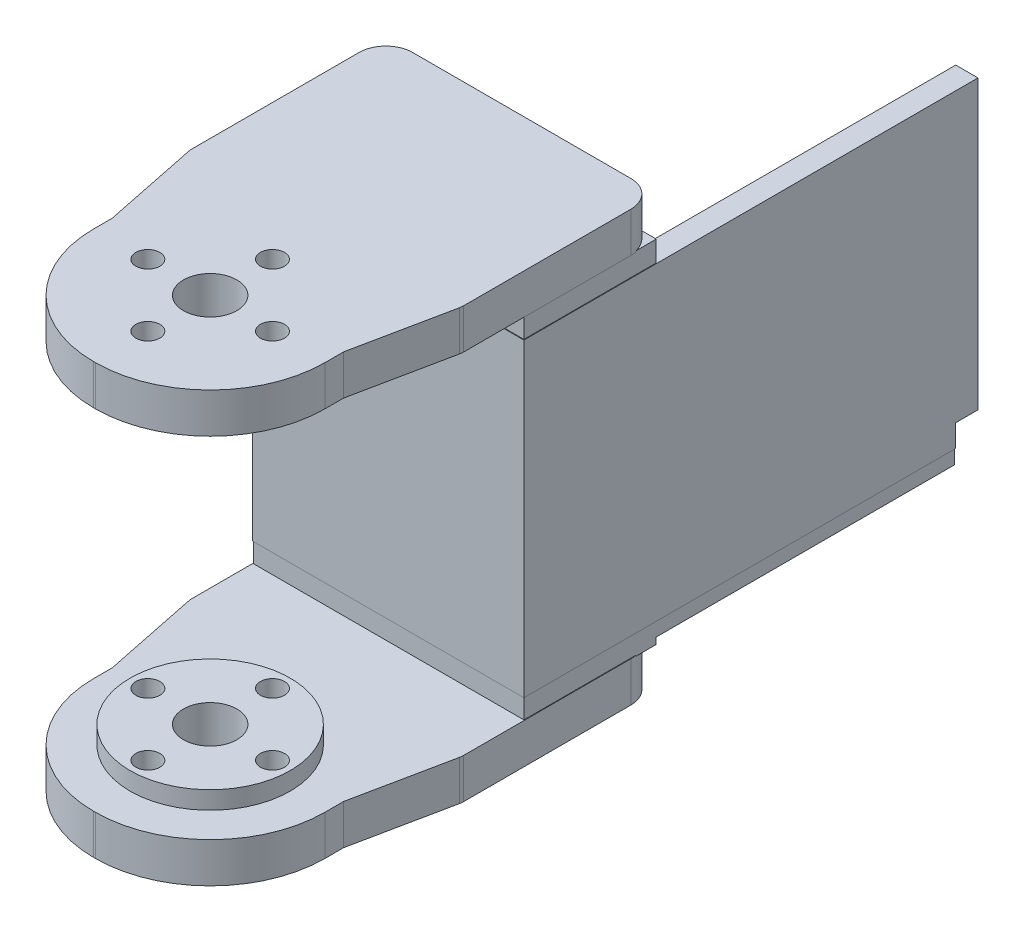
SolidWorks part; units mm, degrees
ref_plane "Front Plane" through (0, 0, 0) normal (0, 0, 1) x (1, 0, 0)
ref_plane "Top Plane" through (0, 0, 0) normal (0, 1, 0) x (1, 0, 0)
ref_plane "Right Plane" through (0, 0, 0) normal (1, 0, 0) x (0, 0, -1)
ref_plane "PY_p18_625" through (0, 18.625, 0) normal (0, 1, 0) x (1, 0, 0)
sketch "S_prism1" plane through (0, 18.625, 0) normal (0, 1, 0) x (1, 0, 0)
  line L0 (-13, 2) -> (-15.2191, 12.8008)
  line L1 (-15.26, 13.2033) -> (-15.26, 32)
  line L2 (-12.26, 35) -> (12.26, 35)
  line L3 (15.26, 32) -> (15.26, 13.2033)
  line L4 (15.2191, 12.8008) -> (13, 2)
  line L5 (13, 2) -> (13, -0.1)
  line L6 (0.1, -13) -> (-0.1, -13)
  line L7 (-13, -0.1) -> (-13, 2)
  arc A0 (-15.2191, 12.8008) -> (-15.26, 13.2033) centre (-13.2498, 13.2042) cw
  arc A1 (-15.26, 32) -> (-12.26, 35) centre (-12.2599, 31.9999) cw
  arc A2 (12.26, 35) -> (15.26, 32) centre (12.2599, 31.9999) cw
  arc A3 (15.26, 13.2033) -> (15.2191, 12.8008) centre (13.2498, 13.2042) cw
  arc A4 (13, -0.1) -> (0.1, -13) centre (0.1001, -0.1001) cw
  arc A5 (-0.1, -13) -> (-13, -0.1) centre (-0.1001, -0.1001) cw
extrude "Boss_1" add sketch "S_prism1" along normal blind 4.5
ref_plane "PY_m20_625" through (0, -20.625, 0) normal (0, 1, 0) x (1, 0, 0)
sketch "S_cyl2" plane through (0, -20.625, 0) normal (0, 1, 0) x (1, 0, 0)
  circle A0 centre (0, 0) radius 9
  dimension "D1_S_cyl2" = 18
extrude "Boss_2" add sketch "S_cyl2" along normal blind 2
ref_plane "PY_m25_125" through (0, -25.125, 0) normal (0, 1, 0) x (1, 0, 0)
sketch "S_prism3" plane through (0, -25.125, 0) normal (0, 1, 0) x (1, 0, 0)
  line L0 (-13, 2) -> (-15.2191, 12.8008)
  line L1 (-15.26, 13.2033) -> (-15.26, 32)
  line L2 (-12.26, 35) -> (12.26, 35)
  line L3 (15.26, 32) -> (15.26, 13.2033)
  line L4 (15.2191, 12.8008) -> (13, 2)
  line L5 (13, 2) -> (13, -0.1)
  line L6 (0.1, -13) -> (-0.1, -13)
  line L7 (-13, -0.1) -> (-13, 2)
  arc A0 (-15.2191, 12.8008) -> (-15.26, 13.2033) centre (-13.2498, 13.2042) cw
  arc A1 (-15.26, 32) -> (-12.26, 35) centre (-12.2599, 31.9999) cw
  arc A2 (12.26, 35) -> (15.26, 32) centre (12.2599, 31.9999) cw
  arc A3 (15.26, 13.2033) -> (15.2191, 12.8008) centre (13.2498, 13.2042) cw
  arc A4 (13, -0.1) -> (0.1, -13) centre (0.1001, -0.1001) cw
  arc A5 (-0.1, -13) -> (-13, -0.1) centre (-0.1001, -0.1001) cw
extrude "Boss_3" add sketch "S_prism3" along normal blind 4.5
ref_plane "PZ_m22_490" through (0, 0, -22.49) normal (0, 0, 1) x (1, 0, 0)
sketch "S_box4" plane through (0, 0, -22.49) normal (0, 0, 1) x (1, 0, 0)
  line L0 (-15.26, -18.4) -> (15.26, -18.4)
  line L1 (15.26, -18.4) -> (15.26, 16.4)
  line L2 (15.26, 16.4) -> (-15.26, 16.4)
  line L3 (-15.26, 16.4) -> (-15.26, -18.4)
  dimension "P1" = 15.26
  dimension "P2" = 18.4
  dimension "P3" = 15.26
  dimension "P4" = 18.4
  dimension "P5" = 15.26
  dimension "P6" = 16.4
  dimension "P7" = 15.26
  dimension "P8" = 16.4
extrude "Boss_4" add sketch "S_box4" along normal blind 2.5
ref_plane "PZ_m71_010" through (0, 0, -71.01) normal (0, 0, 1) x (1, 0, 0)
sketch "S_box5" plane through (0, 0, -71.01) normal (0, 0, 1) x (1, 0, 0)
  line L0 (12.76, -18.4) -> (15.26, -18.4)
  line L1 (15.26, -18.4) -> (15.26, 16.4)
  line L2 (15.26, 16.4) -> (12.76, 16.4)
  line L3 (12.76, 16.4) -> (12.76, -18.4)
  dimension "P1" = 12.76
  dimension "P2" = 18.4
  dimension "P3" = 15.26
  dimension "P4" = 18.4
  dimension "P5" = 15.26
  dimension "P6" = 16.4
  dimension "P7" = 12.76
  dimension "P8" = 16.4
extrude "Boss_5" add sketch "S_box5" along normal blind 51.02
sketch "S_box6" plane through (0, 0, -71.01) normal (0, 0, 1) x (1, 0, 0)
  line L0 (-15.26, -18.4) -> (15.26, -18.4)
  line L1 (15.26, -18.4) -> (15.26, -16)
  line L2 (15.26, -16) -> (-15.26, -16)
  line L3 (-15.26, -16) -> (-15.26, -18.4)
  dimension "P1" = 15.26
  dimension "P2" = 18.4
  dimension "P3" = 15.26
  dimension "P4" = 18.4
  dimension "P5" = 15.26
  dimension "P6" = 16
  dimension "P7" = 15.26
  dimension "P8" = 16
extrude "Boss_6" add sketch "S_box6" along normal blind 51.02
ref_plane "PZ_m38_000" through (0, 0, -38) normal (0, 0, 1) x (1, 0, 0)
sketch "S_box7" plane through (0, 0, -38) normal (0, 0, 1) x (1, 0, 0)
  line L0 (-15.26, -18.4) -> (-12.76, -18.4)
  line L1 (-12.76, -18.4) -> (-12.76, 16.4)
  line L2 (-12.76, 16.4) -> (-15.26, 16.4)
  line L3 (-15.26, 16.4) -> (-15.26, -18.4)
  dimension "P1" = 15.26
  dimension "P2" = 18.4
  dimension "P3" = 12.76
  dimension "P4" = 18.4
  dimension "P5" = 12.76
  dimension "P6" = 16.4
  dimension "P7" = 15.26
  dimension "P8" = 16.4
extrude "Boss_7" add sketch "S_box7" along normal blind 18.01
ref_plane "PZ_m34_930" through (0, 0, -34.93) normal (0, 0, 1) x (1, 0, 0)
sketch "S_box8" plane through (0, 0, -34.93) normal (0, 0, 1) x (1, 0, 0)
  line L0 (-15.19, 16.05) -> (15.19, 16.05)
  line L1 (15.19, 16.05) -> (15.19, 18.725)
  line L2 (15.19, 18.725) -> (-15.19, 18.725)
  line L3 (-15.19, 18.725) -> (-15.19, 16.05)
  dimension "P1" = 15.19
  dimension "P2" = 16.05
  dimension "P3" = 15.19
  dimension "P4" = 16.05
  dimension "P5" = 15.19
  dimension "P6" = 18.725
  dimension "P7" = 15.19
  dimension "P8" = 18.725
extrude "Boss_8" add sketch "S_box8" along normal blind 14.87
sketch "S_box9" plane through (0, 0, -34.93) normal (0, 0, 1) x (1, 0, 0)
  line L0 (-15.19, -20.725) -> (15.19, -20.725)
  line L1 (15.19, -20.725) -> (15.19, -18.3)
  line L2 (15.19, -18.3) -> (-15.19, -18.3)
  line L3 (-15.19, -18.3) -> (-15.19, -20.725)
  dimension "P1" = 15.19
  dimension "P2" = 20.725
  dimension "P3" = 15.19
  dimension "P4" = 20.725
  dimension "P5" = 15.19
  dimension "P6" = 18.3
  dimension "P7" = 15.19
  dimension "P8" = 18.3
extrude "Boss_9" add sketch "S_box9" along normal blind 14.87
ref_plane "PZ_m58_000" through (0, 0, -58) normal (0, 0, 1) x (1, 0, 0)
sketch "S_box10" plane through (0, 0, -58) normal (0, 0, 1) x (1, 0, 0)
  line L0 (-15.19, -20) -> (15.19, -20)
  line L1 (15.19, -20) -> (15.19, -18.35)
  line L2 (15.19, -18.35) -> (-15.19, -18.35)
  line L3 (-15.19, -18.35) -> (-15.19, -20)
  dimension "P1" = 15.19
  dimension "P2" = 20
  dimension "P3" = 15.19
  dimension "P4" = 20
  dimension "P5" = 15.19
  dimension "P6" = 18.35
  dimension "P7" = 15.19
  dimension "P8" = 18.35
extrude "Boss_10" add sketch "S_box10" along normal blind 37.94
ref_plane "PZ_m68_440" through (0, 0, -68.44) normal (0, 0, 1) x (1, 0, 0)
sketch "S_box11" plane through (0, 0, -68.44) normal (0, 0, 1) x (1, 0, 0)
  line L0 (-15.19, -20) -> (-9.6, -20)
  line L1 (-9.6, -20) -> (-9.6, -18.35)
  line L2 (-9.6, -18.35) -> (-15.19, -18.35)
  line L3 (-15.19, -18.35) -> (-15.19, -20)
  dimension "P1" = 15.19
  dimension "P2" = 20
  dimension "P3" = 9.6
  dimension "P4" = 20
  dimension "P5" = 9.6
  dimension "P6" = 18.35
  dimension "P7" = 15.19
  dimension "P8" = 18.35
extrude "Boss_11" add sketch "S_box11" along normal blind 10.54
sketch "S_box12" plane through (0, 0, -68.44) normal (0, 0, 1) x (1, 0, 0)
  line L0 (9.6, -20) -> (15.19, -20)
  line L1 (15.19, -20) -> (15.19, -18.35)
  line L2 (15.19, -18.35) -> (9.6, -18.35)
  line L3 (9.6, -18.35) -> (9.6, -20)
  dimension "P1" = 9.6
  dimension "P2" = 20
  dimension "P3" = 15.19
  dimension "P4" = 20
  dimension "P5" = 15.19
  dimension "P6" = 18.35
  dimension "P7" = 9.6
  dimension "P8" = 18.35
extrude "Boss_12" add sketch "S_box12" along normal blind 10.54
ref_plane "PY_p18_525" through (0, 18.525, 0) normal (0, 1, 0) x (1, 0, 0)
sketch "S_hole13" plane through (0, 18.525, 0) normal (0, 1, 0) x (1, 0, 0)
  circle A0 centre (0, 0) radius 3
  dimension "D1_S_hole13" = 6
extrude "Hole_13" cut sketch "S_hole13" along normal blind 4.7
sketch "S_hole14" plane through (0, 18.525, 0) normal (0, 1, 0) x (1, 0, 0)
  circle A0 centre (7, 0) radius 1.35
  dimension "D1_S_hole14" = 2.7
  dimension "P2" = 7
extrude "Hole_14" cut sketch "S_hole14" along normal blind 4.7
sketch "S_hole15" plane through (0, 18.525, 0) normal (0, 1, 0) x (1, 0, 0)
  circle A0 centre (0, -7) radius 1.35
  dimension "D1_S_hole15" = 2.7
  dimension "P2" = 7
extrude "Hole_15" cut sketch "S_hole15" along normal blind 4.7
sketch "S_hole16" plane through (0, 18.525, 0) normal (0, 1, 0) x (1, 0, 0)
  circle A0 centre (-7, 0) radius 1.35
  dimension "D1_S_hole16" = 2.7
  dimension "P2" = 7
extrude "Hole_16" cut sketch "S_hole16" along normal blind 4.7
sketch "S_hole17" plane through (0, 18.525, 0) normal (0, 1, 0) x (1, 0, 0)
  circle A0 centre (0, 7) radius 1.35
  dimension "D1_S_hole17" = 2.7
  dimension "P2" = 7
extrude "Hole_17" cut sketch "S_hole17" along normal blind 4.7
ref_plane "PY_m25_225" through (0, -25.225, 0) normal (0, 1, 0) x (1, 0, 0)
sketch "S_hole18" plane through (0, -25.225, 0) normal (0, 1, 0) x (1, 0, 0)
  circle A0 centre (0, 0) radius 3
  dimension "D1_S_hole18" = 6
extrude "Hole_18" cut sketch "S_hole18" along normal blind 6.7
sketch "S_hole19" plane through (0, -25.225, 0) normal (0, 1, 0) x (1, 0, 0)
  circle A0 centre (7, 0) radius 1.35
  dimension "D1_S_hole19" = 2.7
  dimension "P2" = 7
extrude "Hole_19" cut sketch "S_hole19" along normal blind 6.7
sketch "S_hole20" plane through (0, -25.225, 0) normal (0, 1, 0) x (1, 0, 0)
  circle A0 centre (0, -7) radius 1.35
  dimension "D1_S_hole20" = 2.7
  dimension "P2" = 7
extrude "Hole_20" cut sketch "S_hole20" along normal blind 6.7
sketch "S_hole21" plane through (0, -25.225, 0) normal (0, 1, 0) x (1, 0, 0)
  circle A0 centre (-7, 0) radius 1.35
  dimension "D1_S_hole21" = 2.7
  dimension "P2" = 7
extrude "Hole_21" cut sketch "S_hole21" along normal blind 6.7
sketch "S_hole22" plane through (0, -25.225, 0) normal (0, 1, 0) x (1, 0, 0)
  circle A0 centre (0, 7) radius 1.35
  dimension "D1_S_hole22" = 2.7
  dimension "P2" = 7
extrude "Hole_22" cut sketch "S_hole22" along normal blind 6.7
ref_plane "PY_m18_500" through (0, -18.5, 0) normal (0, 1, 0) x (1, 0, 0)
sketch "S_hole23" plane through (0, -18.5, 0) normal (0, 1, 0) x (1, 0, 0)
  circle A0 centre (0, 58) radius 11
  dimension "D1_S_hole23" = 22
  dimension "P2" = 58
extrude "Hole_23" cut sketch "S_hole23" along normal blind 2.6
sketch "S_hole24" plane through (0, -18.5, 0) normal (0, 1, 0) x (1, 0, 0)
  circle A0 centre (10.25, 49.7) radius 1.1
  dimension "D1_S_hole24" = 2.2
  dimension "P2" = 10.25
  dimension "P3" = 49.7
extrude "Hole_24" cut sketch "S_hole24" along normal blind 2.6
sketch "S_hole25" plane through (0, -18.5, 0) normal (0, 1, 0) x (1, 0, 0)
  circle A0 centre (-10.25, 25.25) radius 1.1
  dimension "D1_S_hole25" = 2.2
  dimension "P2" = 10.25
  dimension "P3" = 25.25
extrude "Hole_25" cut sketch "S_hole25" along normal blind 2.6
sketch "S_hole26" plane through (0, -18.5, 0) normal (0, 1, 0) x (1, 0, 0)
  circle A0 centre (10.25, 25.25) radius 1.1
  dimension "D1_S_hole26" = 2.2
  dimension "P2" = 10.25
  dimension "P3" = 25.25
extrude "Hole_26" cut sketch "S_hole26" along normal blind 2.6
ref_plane "PZ_m71_110" through (0, 0, -71.11) normal (0, 0, 1) x (1, 0, 0)
sketch "S_cut27" plane through (0, 0, -71.11) normal (0, 0, 1) x (1, 0, 0)
  line L0 (-15.36, -18.5) -> (15.36, -18.5)
  line L1 (15.36, -18.5) -> (15.36, -15.9)
  line L2 (15.36, -15.9) -> (-15.36, -15.9)
  line L3 (-15.36, -15.9) -> (-15.36, -18.5)
  dimension "P1" = 15.36
  dimension "P2" = 18.5
  dimension "P3" = 15.36
  dimension "P4" = 18.5
  dimension "P5" = 15.36
  dimension "P6" = 15.9
  dimension "P7" = 15.36
  dimension "P8" = 15.9
extrude "Pocket_27" cut sketch "S_cut27" along normal blind 2.6
sketch "S_hole28" plane through (0, -25.225, 0) normal (0, 1, 0) x (1, 0, 0)
  circle A0 centre (-10.25, 25.25) radius 2.5
  dimension "D1_S_hole28" = 5
  dimension "P2" = 10.25
  dimension "P3" = 25.25
extrude "Hole_28" cut sketch "S_hole28" along normal blind 5.175
sketch "S_hole29" plane through (0, -25.225, 0) normal (0, 1, 0) x (1, 0, 0)
  circle A0 centre (10.25, 25.25) radius 2.5
  dimension "D1_S_hole29" = 5
  dimension "P2" = 10.25
  dimension "P3" = 25.25
extrude "Hole_29" cut sketch "S_hole29" along normal blind 5.175
ref_plane "PY_m20_100" through (0, -20.1, 0) normal (0, 1, 0) x (1, 0, 0)
sketch "S_hole30" plane through (0, -20.1, 0) normal (0, 1, 0) x (1, 0, 0)
  circle A0 centre (0, 58) radius 10
  dimension "D1_S_hole30" = 20
  dimension "P2" = 58
extrude "Hole_30" cut sketch "S_hole30" along normal blind 1.8
sketch "S_hole31" plane through (0, -20.1, 0) normal (0, 1, 0) x (1, 0, 0)
  circle A0 centre (10.25, 49.7) radius 1.1
  dimension "D1_S_hole31" = 2.2
  dimension "P2" = 10.25
  dimension "P3" = 49.7
extrude "Hole_31" cut sketch "S_hole31" along normal blind 1.8
sketch "S_hole32" plane through (0, -20.1, 0) normal (0, 1, 0) x (1, 0, 0)
  circle A0 centre (10.25, 49.7) radius 2.1
  dimension "D1_S_hole32" = 4.2
  dimension "P2" = 10.25
  dimension "P3" = 49.7
extrude "Hole_32" cut sketch "S_hole32" along normal blind 1.7
sketch "S_hole33" plane through (0, -20.1, 0) normal (0, 1, 0) x (1, 0, 0)
  circle A0 centre (-10.25, 25.25) radius 1.1
  dimension "D1_S_hole33" = 2.2
  dimension "P2" = 10.25
  dimension "P3" = 25.25
extrude "Hole_33" cut sketch "S_hole33" along normal blind 1.8
sketch "S_hole34" plane through (0, -20.1, 0) normal (0, 1, 0) x (1, 0, 0)
  circle A0 centre (-10.25, 25.25) radius 2.1
  dimension "D1_S_hole34" = 4.2
  dimension "P2" = 10.25
  dimension "P3" = 25.25
extrude "Hole_34" cut sketch "S_hole34" along normal blind 1.7
sketch "S_hole35" plane through (0, -20.1, 0) normal (0, 1, 0) x (1, 0, 0)
  circle A0 centre (10.25, 25.25) radius 1.1
  dimension "D1_S_hole35" = 2.2
  dimension "P2" = 10.25
  dimension "P3" = 25.25
extrude "Hole_35" cut sketch "S_hole35" along normal blind 1.8
sketch "S_hole36" plane through (0, -20.1, 0) normal (0, 1, 0) x (1, 0, 0)
  circle A0 centre (10.25, 25.25) radius 2.1
  dimension "D1_S_hole36" = 4.2
  dimension "P2" = 10.25
  dimension "P3" = 25.25
extrude "Hole_36" cut sketch "S_hole36" along normal blind 1.7
equation "\"plate_t\" = 3"
equation "\"clearance\" = 0.4"
